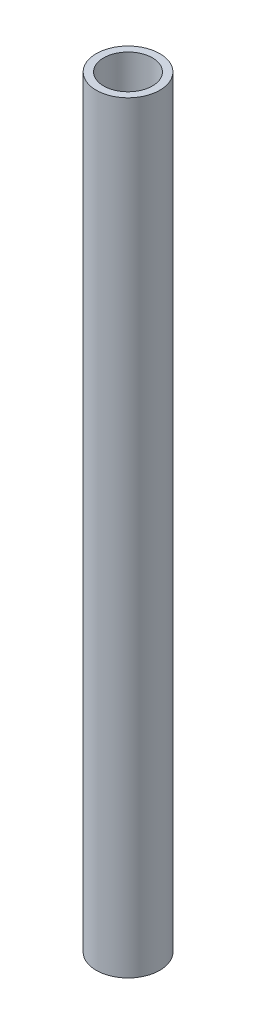
SolidWorks part; units mm, degrees
material "AISI 4130 Steel, annealed at 865C"
ref_plane "X-Y Datum" through (0, 0, 0) normal (0, 0, 1) x (1, 0, 0)
ref_plane "X-Z Datum" through (0, 0, 0) normal (0, 1, 0) x (1, 0, 0)
ref_plane "Y-Z Datum" through (0, 0, 0) normal (1, 0, 0) x (0, 0, -1)
sketch "Sketch1" plane through (0, 0, 0) normal (0, 1, 0) x (1, 0, 0)
  circle A0 centre (0, 0) radius 6.35
  circle A1 centre (0, 0) radius 4.8768
  dimension "D1" = 12.7
  dimension "D2" = 1.4732
extrude "Boss-Extrude1" add sketch "Sketch1" along normal blind 152.4
